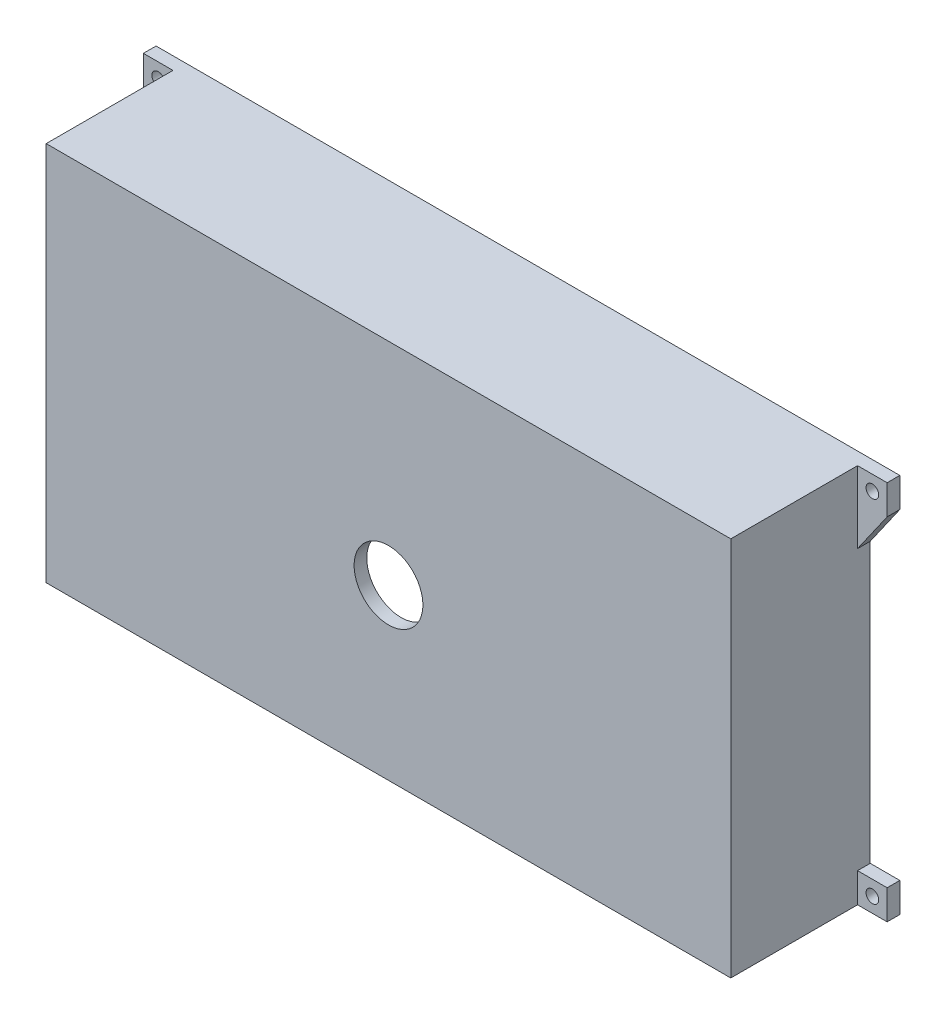
SolidWorks part; units mm, degrees
ref_plane "Front Plane" through (0, 0, 0) normal (0, 0, 1) x (1, 0, 0)
ref_plane "Top Plane" through (0, 0, 0) normal (0, 1, 0) x (1, 0, 0)
ref_plane "Right Plane" through (0, 0, 0) normal (1, 0, 0) x (0, 0, -1)
sketch "Sketch1" plane through (0, 0, 0) normal (0, 0, 1) x (1, 0, 0)
  line L1 (0, 0) -> (162, 0)
  line L3 (0, 90) -> (162, 90)
  line L4 (162, 0) -> (162, 90)
  line L5 (162, 90) -> (169, 90)
  line L6 (162, 90) -> (162, 83)
  line L8 (169, 90) -> (169, 83)
  line L9 (81, 90) -> (81, 0) construction
  line L10 (0, 45) -> (162, 45) construction
  line L11 (169, 0) -> (169, 7)
  line L12 (162, 7) -> (169, 7)
  line L13 (162, 0) -> (162, 7)
  line L14 (162, 0) -> (169, 0)
  line L15 (0, 0) -> (-7, 0)
  line L16 (0, 0) -> (0, 7)
  line L17 (0, 7) -> (-7, 7)
  line L18 (-7, 0) -> (-7, 7)
  line L19 (-7, 90) -> (-7, 83)
  line L21 (0, 90) -> (0, 83)
  line L22 (0, 90) -> (-7, 90)
  line L23 (0, 73) -> (0, 7)
  line L24 (162, 83) -> (162, 73)
  line L25 (0, 83) -> (0, 73)
  line L26 (0, 73) -> (-7, 83)
  line L27 (162, 73) -> (169, 83)
  circle A0 centre (165.5, 86.5) radius 1.5
  circle A1 centre (165.5, 3.5) radius 1.5
  circle A2 centre (-3.5, 3.5) radius 1.5
  circle A3 centre (-3.5, 86.5) radius 1.5
  point P33 (0, 0)
  dimension "D1" = 162
  dimension "D2" = 90
  dimension "D3" = 7
  dimension "D4" = 7
extrude "Boss-Extrude1" add sketch "Sketch1" along normal blind 33 contours L1 L4 L3 region at (81, 45, 0)
extrude "Boss-Extrude2" add sketch "Sketch1<4>" along normal blind 3 contours A3 L22 | A3 L22 L19 | L18 L15 L17 A2 | L4 L14 L11 L12 A1 | A0 L8 L5 | A0 L5 L4 region at (-3.5, 0.099, 0) region at (162.099, 3.5, 0) region at (-2.9692, 83.3912, 0) region at (164.9692, 83.3912, 0)
sketch "Sketch1<4>" plane through (0, 0, 0) normal (0, 0, 1) x (1, 0, 0) same geometry as "Sketch1"
sketch "Sketch3" plane through (0, 0, 0) normal (0, 0, -1) x (-1, 0, 0)
  line L0 (0, 90) -> (-162, 90) construction
  line L5 (0, 0) -> (0, 90) construction
  line L6 (-159, 87) -> (-3, 87)
  line L7 (-159, 87) -> (-159, 0)
  line L8 (-159, 0) -> (-3, 0)
  line L9 (-3, 87) -> (-3, 0)
  line L10 (-162, 0) -> (-162, 90) construction
  line L11 (-81, 87) -> (-81, 0) construction
  line L12 (7, 90) -> (-169, 90) construction
  circle A0 centre (-81, 40) radius 8.1377
  point P6 (-81, 40)
  dimension "D5" = 50
  dimension "D1" = 3
  dimension "D2" = 3
  dimension "D3" = 3
  dimension "D4" = 87
extrude "Cut-Extrude1" cut sketch "Sketch3" against normal blind 30
extrude "Cut-Extrude2" cut sketch "Sketch3<2>" against normal blind 33 contours A0
sketch "Sketch3<2>" plane through (0, 0, 0) normal (0, 0, -1) x (-1, 0, 0) same geometry as "Sketch3"
